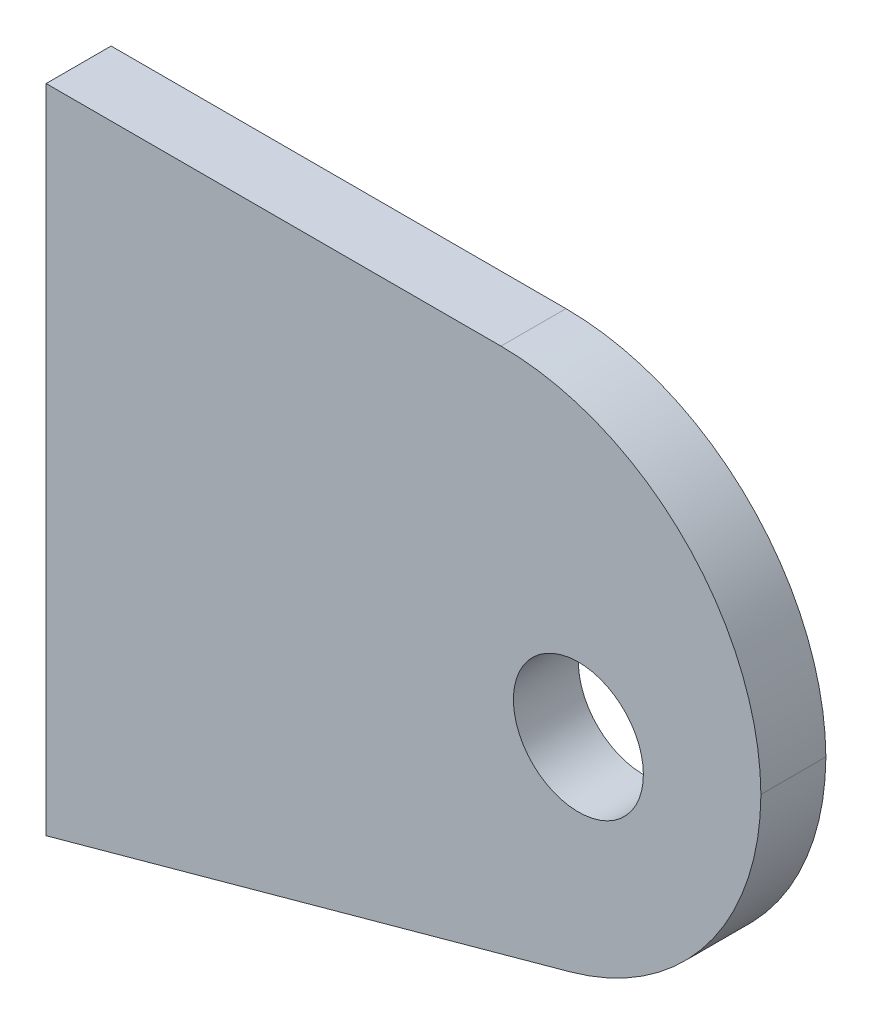
SolidWorks part; units mm, degrees
material "AISI 4340 Steel, annealed"
ref_plane "X-Y Datum" through (0, 0, 0) normal (0, 0, 1) x (1, 0, 0)
ref_plane "X-Z Datum" through (0, 0, 0) normal (0, 1, 0) x (1, 0, 0)
ref_plane "Y-Z Datum" through (0, 0, 0) normal (1, 0, 0) x (0, 0, -1)
sketch "Sketch1" plane through (0, 0, 0) normal (0, 0, 1) x (1, 0, 0)
  line L1 (-26.2895, 30.6046) -> (34.1686, 30.6046)
  line L2 (-26.2895, 30.6046) -> (-26.2895, -30.6046)
  line L3 (-26.2895, -30.6046) -> (34.1686, -30.6046)
  line L4 (34.1686, 30.6046) -> (34.1686, -30.6046)
  point P4 (-26.2895, 0)
extrude "Boss-Extrude1" add sketch "Sketch1" along normal blind 3.175
hole_wizard "1/4 (0.25) Diameter Hole1" positions "Sketch2" profile "Sketch3" hole size "1/4" standard "ANSI Inch"
sketch "Sketch2" plane through (0, 0, 3.175) normal (0, 0, 1) x (1, 0, 0)
  point P0 (-0.2824, 15.9554)
  dimension "D1" = 26.0071
  dimension "D2" = 14.6492
sketch "Sketch3" plane through (-0.2824, 15.9554, 3.175) normal (1, 0, 0) x (0, -1, 0)
  line L0 (0, 0) -> (0, 11.176)
  line L1 (0, 11.176) -> (3.175, 9.2683)
  line L2 (3.175, 9.2683) -> (3.175, 0)
  line L5 (3.175, 0) -> (0, 0)
  line L10 (0, 11.176) -> (-3.175, 9.2683) construction
  line L11 (0, -6.35) -> (0, 107.95) construction
  dimension "Hole Dia." = 6.35
  dimension "Hole Depth" = 11.176
  dimension "Drill Angle" = 118
sketch "Sketch4" plane through (0, 0, 0) normal (0, 0, -1) x (-1, 0, 0)
  line L0 (-8.6355, 8.3796) -> (-8.6355, 30.6046)
  line L6 (26.2895, -1.2247) -> (26.2895, 30.6046)
  line L7 (-8.6355, 30.6046) -> (26.2895, 30.6046)
  line L8 (-8.6355, 8.3796) -> (26.2895, -1.2247)
  point P3 (0, 0)
  line M8 (26.2895, 30.6046) -> (-34.1686, 30.6046)
  line M9 (-34.1686, 30.6046) -> (-34.1686, -30.6046)
  line M10 (-34.1686, -30.6046) -> (26.2895, -30.6046)
  dimension "D1" = 34.925
  dimension "D3" = 22.225
  dimension "D4" = 31.8292
extrude "Cut-Extrude1" cut sketch "Sketch4" against normal through all contours L8 L0 M8 M9 M10
fillet "Fillet1" radius 12.7 2 edges at (8.6355, 30.6046, 1.5875) (8.6355, 8.3796, 1.5875)
